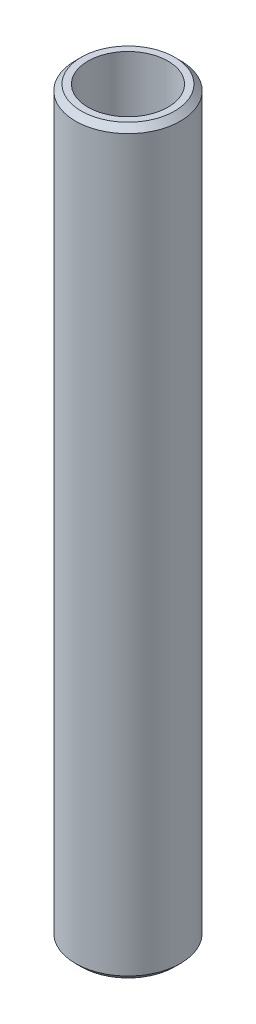
SolidWorks part; units mm, degrees
ref_plane "Front Plane" through (0, 0, 0) normal (0, 0, 1) x (1, 0, 0)
ref_plane "Top Plane" through (0, 0, 0) normal (0, 1, 0) x (1, 0, 0)
ref_plane "Right Plane" through (0, 0, 0) normal (1, 0, 0) x (0, 0, -1)
sketch "Sketch1" plane through (0, 0, 0) normal (0, 1, 0) x (1, 0, 0)
  circle A0 centre (0, 0) radius 42.5
  dimension "SHAFT_OD" = 85
extrude "Boss-Extrude1" add sketch "Sketch1" along normal blind 600
sketch "Sketch2" plane through (0, 0, 0) normal (0, 1, 0) x (1, 0, 0)
  circle A0 centre (0, 0) radius 32.388
  dimension "BORE_D" = 64.776
extrude "Cut-Extrude1" cut sketch "Sketch2" along normal through all
chamfer "Chamfer1" distance 4.6993 angle 45 2 edges at (0, 600, 42.5) (0, 0, 42.5)
